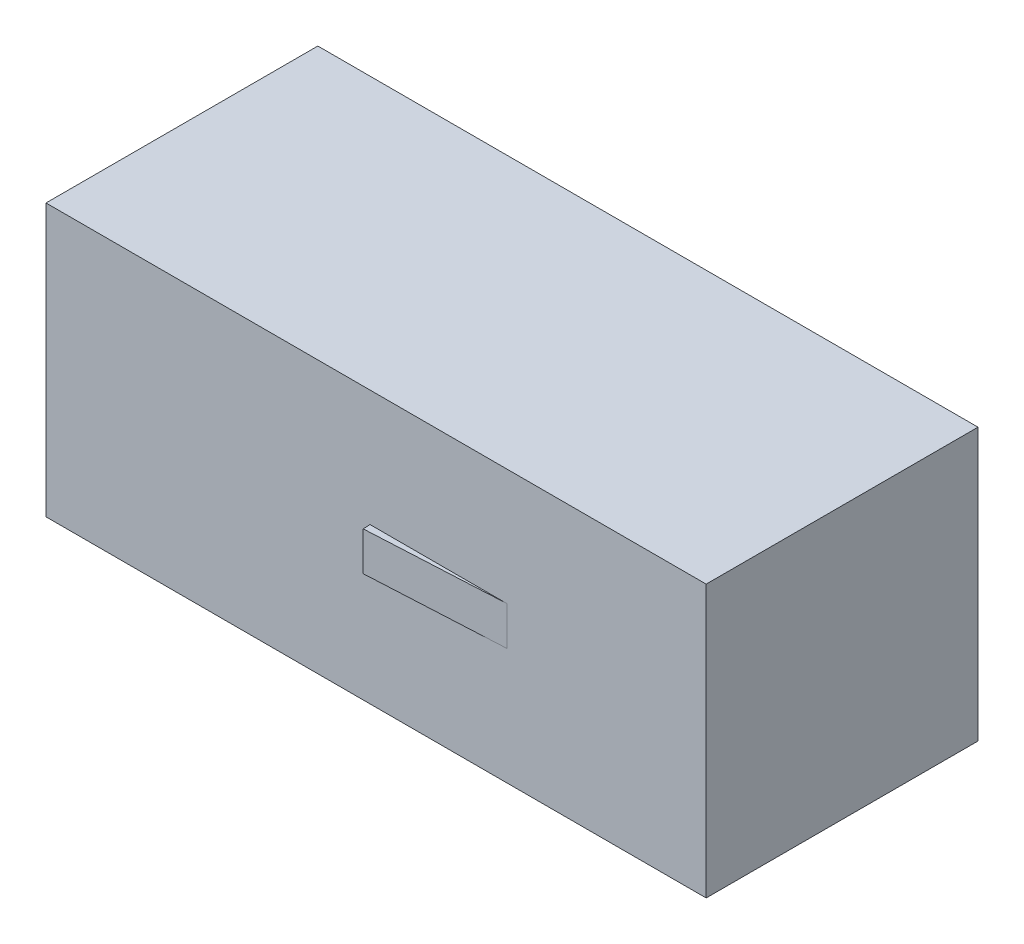
SolidWorks part; units mm, degrees
ref_plane "Front Plane" through (0, 0, 0) normal (0, 0, 1) x (1, 0, 0)
ref_plane "Top Plane" through (0, 0, 0) normal (0, 1, 0) x (1, 0, 0)
ref_plane "Right Plane" through (0, 0, 0) normal (1, 0, 0) x (0, 0, -1)
sketch "Эскиз1" plane through (0, 0, 0) normal (0, 0, 1) x (1, 0, 0)
  line L1 (-85, -35) -> (85, -35)
  line L2 (-85, -35) -> (-85, 35)
  line L3 (-85, 35) -> (85, 35)
  line L4 (85, -35) -> (85, 35)
  line L5 (-85, -35) -> (85, 35) construction
  line L6 (-85, 35) -> (85, -35) construction
  point P0 (0, 0)
  dimension "D1" = 70
  dimension "D2" = 170
extrude "Бобышка-Вытянуть1" add sketch "Эскиз1" along normal mid plane 70
sketch "Эскиз2" plane through (0, -35, 0) normal (0, -1, 0) x (1, 0, 0)
  line L0 (33.7136, 35) -> (-1.569, 35)
  line L1 (-85, 35) -> (85, 35) construction
  line L3 (-1.4724, 36.844) -> (33.7136, 35)
  line L6 (-1.4724, 36.844) -> (-1.569, 35)
  point P4 (-1.4906, 35)
  dimension "D1" = 3
  dimension "D2" = 90
extrude "Бобышка-Вытянуть2" add sketch "Эскиз2" along normal mid plane 10 from offset 35 offset against normal yes
